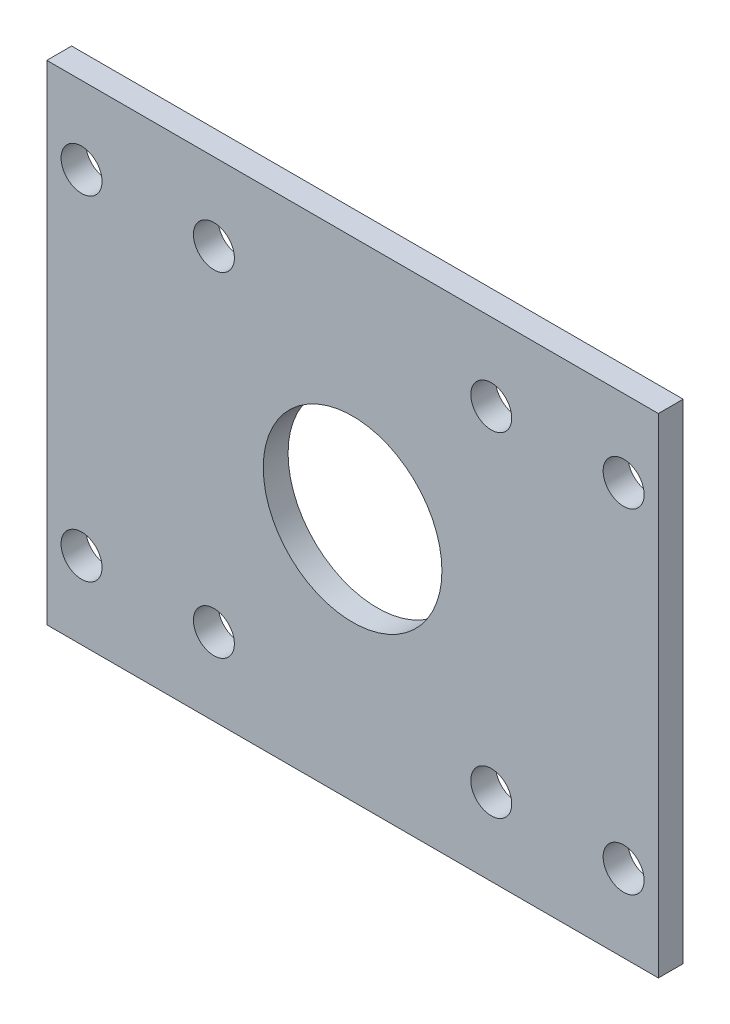
SolidWorks part; units mm, degrees
ref_plane "Front Plane" through (0, 0, 0) normal (0, 0, 1) x (1, 0, 0)
ref_plane "Top Plane" through (0, 0, 0) normal (0, 1, 0) x (1, 0, 0)
ref_plane "Right Plane" through (0, 0, 0) normal (1, 0, 0) x (0, 0, -1)
sketch "Sketch2" plane through (0, 0, 0) normal (0, 0, 1) x (1, 0, 0)
  line L0 (-16.3505, -19.698) -> (16.2476, -19.702) construction
  line L1 (16.2524, 19.698) -> (-16.3457, 19.702) construction
  line L2 (23.4456, -19.5874) -> (23.4447, -26.5989) construction
  line L3 (-23.5487, -26.5984) -> (-23.5487, -19.7657) construction
  line L4 (-24.6447, -19.697) -> (24.6447, -19.703)
  line L5 (24.6447, 19.697) -> (-24.6447, 19.703)
  line L6 (23.4456, -19.5874) -> (23.4447, -26.5989) construction
  line L7 (-23.5487, -26.5984) -> (-23.5487, -19.7657) construction
  line L8 (-11.1772, 13.4655) -> (-21.8445, 13.4655) construction
  line L9 (-19.0437, 19.9024) -> (-19.048, -15.0976) construction
  line L10 (-21.8441, 16.6987) -> (-24.6443, 15.0824) construction
  line L11 (-24.6443, 15.0824) -> (-24.6447, 11.8493) construction
  line L12 (-24.6447, 11.8493) -> (-21.8449, 10.2324) construction
  line L13 (-21.8449, 10.2324) -> (-19.0447, 11.8486) construction
  line L14 (-19.0447, 11.8486) -> (-19.0443, 15.0817) construction
  line L15 (-19.0443, 15.0817) -> (-21.8441, 16.6987) construction
  line L16 (-19.0437, 19.9024) -> (-19.048, -15.0976) construction
  line L17 (0, 0) -> (0, 1.3862) construction
  line L18 (0, 0) -> (-1.3911, 0) construction
  line L19 (-24.6447, 19.703) -> (-24.6447, -19.697)
  line L20 (24.6447, 19.697) -> (24.6447, -19.703)
  line L21 (-24.6447, -19.697) -> (24.6447, 19.697) construction
  circle A0 centre (0, 0) radius 7 construction
  circle A1 centre (0, 0) radius 7 construction
  circle A2 centre (0, 0) radius 7.2
  circle A3 centre (11.1772, -13.4655) radius 1.65 construction
  circle A4 centre (-11.1772, -13.4655) radius 1.65 construction
  circle A5 centre (-11.1772, 13.4655) radius 1.65 construction
  circle A6 centre (11.1772, 13.4655) radius 1.65 construction
  circle A7 centre (11.1772, -13.4655) radius 1.65
  circle A8 centre (-11.1772, -13.4655) radius 1.65
  circle A9 centre (-11.1772, 13.4655) radius 1.65
  circle A10 centre (11.1772, 13.4655) radius 1.65
  circle A11 centre (-21.8445, 13.4655) radius 1.6514
  circle A12 centre (-21.8445, 13.4655) radius 2.8 construction
  circle A13 centre (-21.8445, -13.4655) radius 1.6514
  circle A14 centre (21.8445, -13.4655) radius 1.6514
  circle A15 centre (21.8445, 13.4655) radius 1.6514
  point P5 (0, 0)
  point P27 (26.1524, 19.9024)
  dimension "D2" = 5.6
  dimension "D3" = 3.3029
  dimension "D1" = 0.2
extrude "Boss-Extrude1" add sketch "Sketch2" along normal blind 2
